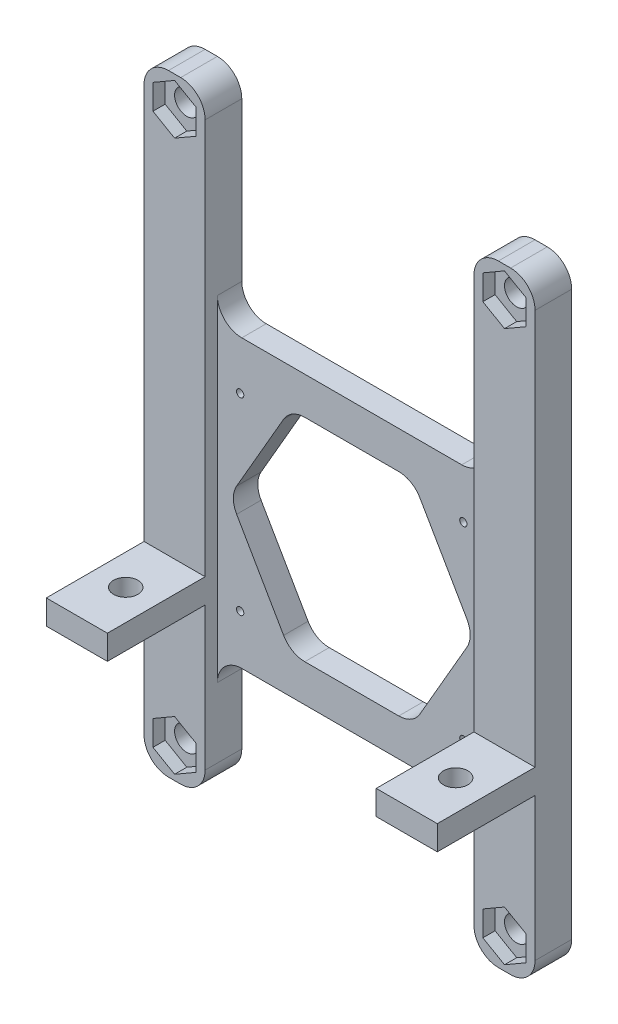
SolidWorks part; units mm, degrees
ref_plane "Front Plane" through (0, 0, 0) normal (0, 0, 1) x (1, 0, 0)
ref_plane "Top Plane" through (0, 0, 0) normal (0, 1, 0) x (1, 0, 0)
ref_plane "Right Plane" through (0, 0, 0) normal (1, 0, 0) x (0, 0, -1)
sketch "Sketch1" plane through (0, 0, 0) normal (0, 0, 1) x (1, 0, 0)
  line L0 (-29, -36) -> (29, -36) construction
  line L1 (-29, -36) -> (-29, 13) construction
  line L2 (29, -36) -> (29, 13) construction
  line L3 (-29, 13) -> (29, 13) construction
  line L4 (29, -36) -> (-29, 13) construction
  line L5 (-29, -36) -> (29, 13) construction
  line L6 (-50.8, -79.5094) -> (50.8, -79.5094) construction
  line L7 (-50.8, -79.5094) -> (-50.8, 79.5094)
  line L8 (50.8, -79.5094) -> (50.8, 79.5094)
  line L9 (-50.8, 79.5094) -> (50.8, 79.5094) construction
  line L10 (-50.8, -79.5094) -> (50.8, 79.5094) construction
  line L11 (50.8, -79.5094) -> (-50.8, 79.5094) construction
  line L12 (-34.925, 25.7) -> (34.925, 25.7)
  line L13 (-0.8, 0) -> (-50.8, 0) construction
  line L14 (-0.8, 0) -> (50.8, 0) construction
  line L15 (-50.8, 68) -> (50.8, 68) construction
  line L18 (-50.8, -68) -> (50.8, -68) construction
  line L21 (0, 68) -> (0, -68) construction
  line L22 (-50.8, 79.5094) -> (-34.925, 79.5094)
  line L23 (-34.925, 79.5094) -> (-34.925, 25.7)
  line L24 (50.8, 79.5094) -> (34.925, 79.5094)
  line L25 (34.925, 79.5094) -> (34.925, 25.7)
  line L26 (-34.925, -48.7) -> (-34.925, -79.5094)
  line L27 (-34.925, -79.5094) -> (-50.8, -79.5094)
  line L28 (-34.925, -48.7) -> (34.925, -48.7)
  line L29 (34.925, -48.7) -> (34.925, -79.5094)
  line L30 (34.925, -79.5094) -> (50.8, -79.5094)
  line L31 (32.5, -39.5) -> (-32.5, -39.5) construction
  line L32 (32.5, -39.5) -> (32.5, 16.5) construction
  line L33 (-32.5, -39.5) -> (-32.5, 16.5) construction
  line L34 (32.5, 16.5) -> (-32.5, 16.5) construction
  line L35 (32.5, -39.5) -> (-32.5, 16.5) construction
  line L36 (-32.5, -39.5) -> (32.5, 16.5) construction
  line L38 (-15.875, -38.9963) -> (15.875, -38.9963)
  line L39 (15.875, -38.9963) -> (31.75, -11.5)
  line L40 (31.75, -11.5) -> (15.875, 15.9963)
  line L41 (15.875, 15.9963) -> (-15.875, 15.9963)
  line L42 (-15.875, 15.9963) -> (-31.75, -11.5)
  line L43 (-31.75, -11.5) -> (-15.875, -38.9963)
  circle A0 centre (29, 13) radius 0.95
  circle A1 centre (29, -36) radius 0.95
  circle A2 centre (-29, -36) radius 0.95
  circle A3 centre (-29, 13) radius 0.95
  circle A10 centre (-42.8625, 71.5719) radius 3.175
  circle A11 centre (42.8625, 71.5719) radius 3.175
  circle A12 centre (-42.8625, -71.5719) radius 3.175
  circle A13 centre (42.8625, -71.5719) radius 3.175
  circle A14 centre (0, -11.5) radius 27.4963 construction
  point P1 (0, 0)
  point P2 (0, 0)
  point P28 (0, -11.5)
  point P35 (0, 25.7)
  point P43 (0, -11.5)
  dimension "D1" = 1.9
  dimension "D7" = 3.5719
  dimension "D9" = 7.9375
  dimension "D12" = 6.35
  dimension "D2" = 58
  dimension "D3" = 49
  dimension "D4" = 136
  dimension "D5" = 101.6
  dimension "D6" = 15.875
  dimension "D8" = 7.9375
  dimension "D10" = 32
  dimension "D11" = 3.5719
  dimension "D13" = 12.7
  dimension "D14" = 12.7
  dimension "D15" = 65
  dimension "D16" = 56
  dimension "D17" = 15.875
  dimension "D18" = 31.75
extrude "Boss-Extrude1" add sketch "Sketch1" along normal blind 6.35
sketch "Sketch2" plane through (0, 0, 6.35) normal (0, 0, 1) x (1, 0, 0)
  line L0 (-50.8, 79.5094) -> (-50.8, -79.5094)
  line L1 (-50.8, 79.5094) -> (-34.925, 79.5094)
  line L2 (-50.8, -79.5094) -> (-34.925, -79.5094)
  line L3 (-34.925, 79.5094) -> (-34.925, -79.5094) construction
  line L4 (0, 38.2822) -> (0, -62.9404) construction
  line L8 (-34.925, -79.5094) -> (-34.925, 79.5094)
  line L16 (34.925, 79.5094) -> (34.925, -79.5094) construction
  line L17 (-48.4875, 68.3243) -> (-42.8625, 65.0767)
  line L18 (-42.8625, 65.0767) -> (-37.2375, 68.3243)
  line L19 (-37.2375, 68.3243) -> (-37.2375, 74.8195)
  line L20 (-37.2375, 74.8195) -> (-42.8625, 78.0671)
  line L21 (-42.8625, 78.0671) -> (-48.4875, 74.8195)
  line L22 (-48.4875, 74.8195) -> (-48.4875, 68.3243)
  line L23 (-37.2375, -68.3243) -> (-42.8625, -65.0767)
  line L24 (-42.8625, -65.0767) -> (-48.4875, -68.3243)
  line L25 (-48.4875, -68.3243) -> (-48.4875, -74.8195)
  line L26 (-48.4875, -74.8195) -> (-42.8625, -78.0671)
  line L27 (-42.8625, -78.0671) -> (-37.2375, -74.8195)
  line L28 (-37.2375, -74.8195) -> (-37.2375, -68.3243)
  line L29 (37.2375, -74.8195) -> (37.2375, -68.3243)
  line L30 (42.8625, -78.0671) -> (37.2375, -74.8195)
  line L31 (48.4875, -74.8195) -> (42.8625, -78.0671)
  line L32 (48.4875, -68.3243) -> (48.4875, -74.8195)
  line L33 (42.8625, -65.0767) -> (48.4875, -68.3243)
  line L34 (37.2375, -68.3243) -> (42.8625, -65.0767)
  line L35 (48.4875, 74.8195) -> (48.4875, 68.3243)
  line L36 (42.8625, 78.0671) -> (48.4875, 74.8195)
  line L37 (37.2375, 74.8195) -> (42.8625, 78.0671)
  line L38 (37.2375, 68.3243) -> (37.2375, 74.8195)
  line L39 (42.8625, 65.0767) -> (37.2375, 68.3243)
  line L40 (48.4875, 68.3243) -> (42.8625, 65.0767)
  line L41 (34.925, -79.5094) -> (34.925, 79.5094)
  line L45 (50.8, -79.5094) -> (34.925, -79.5094)
  line L46 (50.8, 79.5094) -> (34.925, 79.5094)
  line L47 (50.8, 79.5094) -> (50.8, -79.5094)
  circle A0 centre (-42.8625, 71.5719) radius 5.625 construction
  circle A1 centre (-42.8625, -71.5719) radius 5.625 construction
  circle A2 centre (42.8625, -71.5719) radius 5.625 construction
  circle A3 centre (42.8625, 71.5719) radius 5.625 construction
  point P10 (-34.925, -78.0671)
  point P11 (0, 0)
  point P55 (0, 0)
  dimension "D1" = 15.875
  dimension "D2" = 11.25
extrude "Boss-Extrude2" add sketch "Sketch2" along normal blind 3.175
sketch "Sketch3" plane through (0, 0, 9.525) normal (0, 0, 1) x (1, 0, 0)
  line L0 (-34.925, -36) -> (-34.925, -29.65)
  line L1 (-34.925, -36) -> (-50.8, -36)
  line L2 (-34.925, -29.65) -> (-50.8, -29.65)
  line L3 (-50.8, -36) -> (-50.8, -29.65)
  line L5 (-34.925, -48.7) -> (34.925, -48.7) construction
  line L6 (-34.925, -79.5094) -> (-34.925, 79.5094) construction
  line L8 (-50.8, 79.5094) -> (-50.8, -79.5094) construction
  line L9 (0, 0) -> (0, -33.67) construction
  line L10 (50.8, -36) -> (50.8, -29.65)
  line L11 (34.925, -29.65) -> (50.8, -29.65)
  line L12 (34.925, -36) -> (50.8, -36)
  line L13 (34.925, -36) -> (34.925, -29.65)
  dimension "D1" = 6.35
  dimension "D2" = 19.05
extrude "Boss-Extrude3" add sketch "Sketch3" along normal blind 25.4
sketch "Sketch4" plane through (0, -36, 0) normal (0, 1, 0) x (1, 0, 0)
  line L0 (-42.8625, -34.925) -> (-42.8625, -9.525) construction
  line L1 (-34.925, -34.925) -> (-50.8, -34.925) construction
  line L3 (0, 0) -> (0, -31.3873) construction
  line L4 (-50.8, -9.525) -> (-34.925, -9.525) construction
  circle A0 centre (-42.8625, -22.225) radius 3.175
  circle A1 centre (42.8625, -22.225) radius 3.175
  point P6 (0, 0)
  dimension "D1" = 6.35
extrude "Cut-Extrude1" cut sketch "Sketch4" along normal through all
fillet "Fillet2" radius 6.35 18 edges at (34.925, -48.7, 3.175) (-34.925, -48.7, 3.175) (-50.8, -79.5094, 4.7625) (-34.925, -79.5094, 4.7625) (34.925, -79.5094, 4.7625) (50.8, -79.5094, 4.7625) (50.8, 79.5094, 4.7625) (34.925, 79.5094, 4.7625) (34.925, 25.7, 3.175) (-34.925, 25.7, 3.175) (-34.925, 79.5094, 4.7625) (-50.8, 79.5094, 4.7625) (-15.875, 15.9963, 3.175) (-31.75, -11.5, 3.175) (-15.875, -38.9963, 3.175) (15.875, -38.9963, 3.175) (31.75, -11.5, 3.175) (15.875, 15.9963, 3.175)
